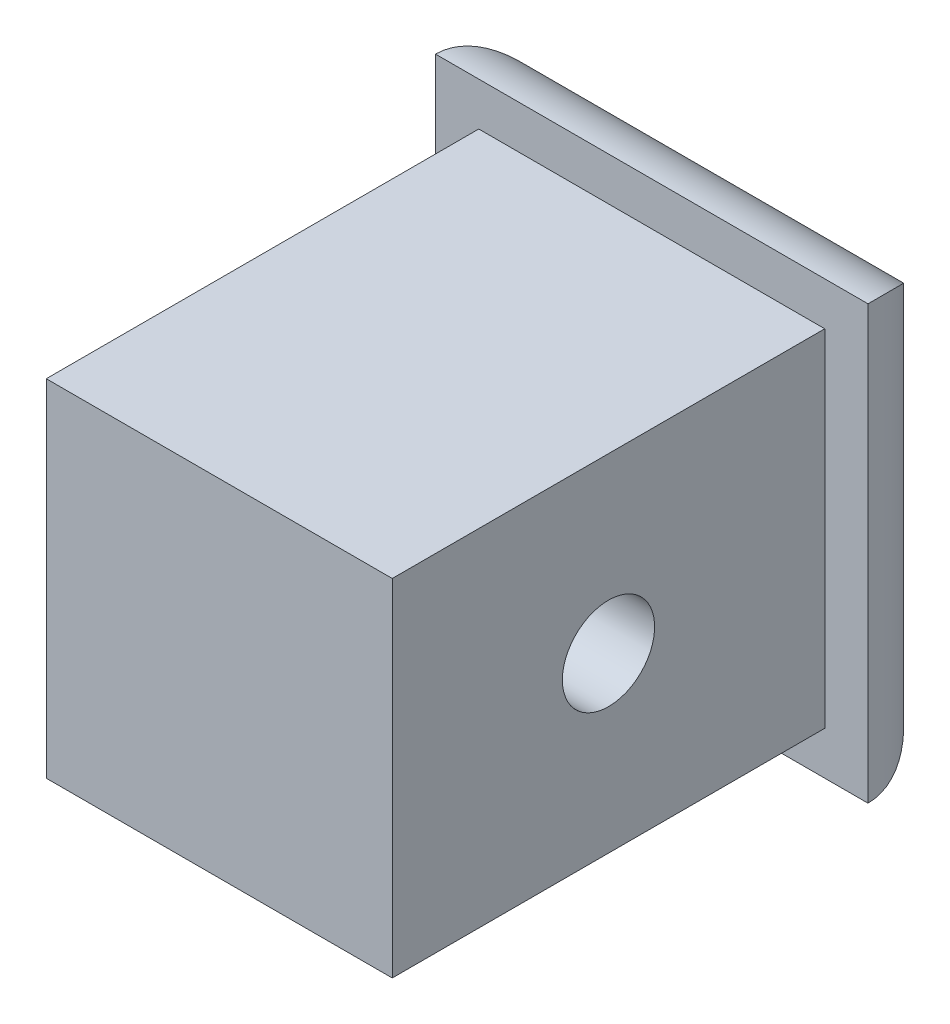
SolidWorks part; units mm, degrees
ref_plane "正面" through (0, 0, 0) normal (0, 0, 1) x (1, 0, 0)
ref_plane "平面" through (0, 0, 0) normal (0, 1, 0) x (1, 0, 0)
ref_plane "右側面" through (0, 0, 0) normal (1, 0, 0) x (0, 0, -1)
sketch "ｽｹｯﾁ8" plane through (0, 0, 0) normal (0, 0, 1) x (1, 0, 0)
  line L1 (-7.5, 7.5) -> (7.5, 7.5)
  line L2 (-7.5, 7.5) -> (-7.5, -7.5)
  line L3 (-7.5, -7.5) -> (7.5, -7.5)
  line L4 (7.5, 7.5) -> (7.5, -7.5)
  line L5 (-7.5, 7.5) -> (7.5, -7.5) construction
  line L6 (-7.5, -7.5) -> (7.5, 7.5) construction
  point P0 (0, 0)
  dimension "D1" = 15
  dimension "D2" = 15
extrude "ﾎﾞｽ - 押し出し3" add sketch "ｽｹｯﾁ8" along normal blind 3
sketch "ｽｹｯﾁ9" plane through (0, 0, 3) normal (0, 0, 1) x (1, 0, 0)
  line L0 (-7.5, 7.5) -> (-7.5, -7.5) construction
  line L1 (-6, 6) -> (6, 6)
  line L2 (-6, 6) -> (-6, -6)
  line L3 (-6, -6) -> (6, -6)
  line L4 (6, 6) -> (6, -6)
  line L5 (-6, 6) -> (6, -6) construction
  line L6 (-6, -6) -> (6, 6) construction
  line L7 (7.5, 7.5) -> (-7.5, 7.5) construction
  point P0 (0, 0)
  dimension "D1" = 1.5
  dimension "D2" = 1.5
extrude "ﾎﾞｽ - 押し出し4" add sketch "ｽｹｯﾁ9" along normal blind 15
sketch "ｽｹｯﾁ10" plane through (-6, 0, 0) normal (-1, 0, 0) x (0, 0, 1)
  line L0 (3, 0) -> (18, 0) construction
  line L1 (3, 6) -> (3, -6) construction
  line L2 (18, 6) -> (18, -6) construction
  line L3 (3, 7.5) -> (3, -7.5) construction
  circle A0 centre (10.5, 0) radius 1.6
  dimension "D1" = 7.5
  dimension "D2" = 3.2
extrude "ｶｯﾄ - 押し出し2" cut sketch "ｽｹｯﾁ10" against normal through all
fillet "ﾌｨﾚｯﾄ2" radius 3 4 edges at (0, 7.5, 0) (-7.5, 0, 0) (0, -7.5, 0) (7.5, 0, 0)
